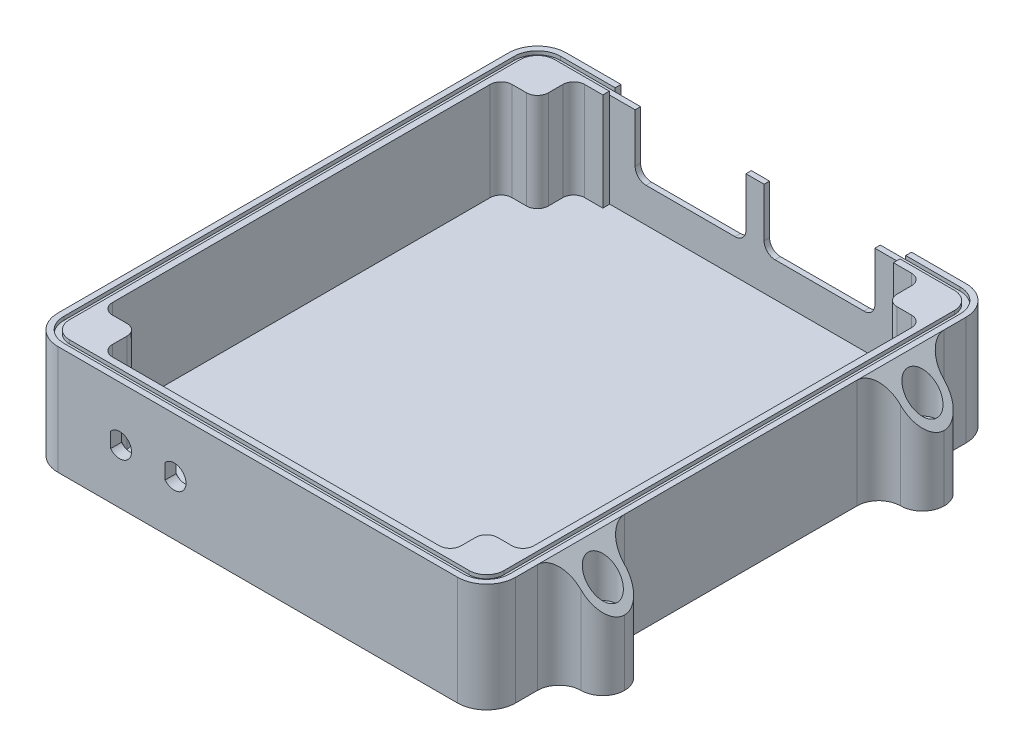
SolidWorks part; units mm, degrees
ref_plane "Front Plane" through (0, 0, 0) normal (0, 0, 1) x (1, 0, 0)
ref_plane "Top Plane" through (0, 0, 0) normal (0, 1, 0) x (1, 0, 0)
ref_plane "Right Plane" through (0, 0, 0) normal (1, 0, 0) x (0, 0, -1)
sketch "Sketch1" plane through (0, 0, 0) normal (0, 1, 0) x (1, 0, 0)
  line L0 (0, 0) -> (0, 94.0944) construction
  line L1 (-63, -70) -> (63, -70)
  line L2 (-63, -70) -> (-63, 70)
  line L3 (-63, 70) -> (63, 70)
  line L4 (63, -70) -> (63, 70)
  line L5 (-63, -70) -> (63, 70) construction
  line L6 (-63, 70) -> (63, -70) construction
  line L7 (63, -50) -> (75, -50)
  line L8 (63, -50) -> (63, -38)
  line L9 (63, -38) -> (75, -38)
  line L10 (75, -50) -> (75, -38)
  line L11 (0, 0) -> (-101.6778, 0) construction
  line L12 (-63, -38) -> (-75, -38)
  line L13 (-75, -50) -> (-75, -38)
  line L14 (-63, -50) -> (-75, -50)
  line L15 (-63, -50) -> (-63, -38)
  line L16 (63, 38) -> (75, 38)
  line L17 (75, 50) -> (75, 38)
  line L18 (63, 50) -> (75, 50)
  line L19 (63, 50) -> (63, 38)
  line L20 (-63, 50) -> (-63, 38)
  line L21 (-63, 50) -> (-75, 50)
  line L22 (-75, 50) -> (-75, 38)
  line L23 (-63, 38) -> (-75, 38)
  point P0 (0, 0)
  dimension "D1" = 140
  dimension "D2" = 126
  dimension "D3" = 12
  dimension "D4" = 12
  dimension "D5" = 20
extrude "Boss-Extrude2" add sketch "Sketch1" along normal blind 30 contours L14 L2 L12 L13 | L1 L4 L3 L2 | L23 L2 L21 L22 | L18 L4 L16 L17 | L7 L10 L9 L4 region at (0, 0, 0) region at (-69, 0, 44) region at (69, 0, 44) region at (-69, 0, -44) region at (69, 0, -44)
sketch "Sketch2" plane through (0, 30, 0) normal (0, 1, 0) x (1, 0, 0)
  line L1 (63, -50) -> (75, -50) construction
  line L3 (0, 0) -> (0, -57.1416) construction
  line L4 (0, 0) -> (45.0651, 0) construction
  line L5 (75, -50) -> (75, -38) construction
  point P0 (69, -44)
  point P5 (-69, -44)
  point P6 (69, 44)
  point P11 (-69, 44)
  dimension "D1" = 6
  dimension "D2" = 6
hole_wizard "CBORE for M4 Hex Socket Head Cap Screw1" positions "3DSketch1" profile "Sketch3" counterbore size "M4" standard "ISO" end condition through all
sketch3d "3DSketch1"
  point P0 (-69, 30, 44)
  point P3 (69, 30, 44)
  point P6 (69, 30, -44)
  point P9 (-69, 30, -44)
sketch "Sketch3" plane through (-69, 30, 44) normal (1, 0, 0) x (0, 0, 1)
  line L0 (0, 0) -> (0, 30)
  line L1 (2.4, 29.4) -> (3, 30)
  line L2 (2.4, 29.4) -> (2.4, 14.4)
  line L3 (2.4, 14.4) -> (4, 14.4)
  line L4 (4, 14.4) -> (4, 0)
  line L5 (4, 0) -> (0, 0)
  line L11 (0, -6.35) -> (0, 107.95) construction
  line L12 (3, 30) -> (0, 30)
  line L13 (-2.4, 29.4) -> (-3, 30) construction
  dimension "Thru Hole Dia." = 4.8
  dimension "Thru Hole Depth" = 30
  dimension "C'Bore Dia." = 8
  dimension "C'Bore Depth" = 14.4
  dimension "Far C'Sink Dia." = 6
  dimension "Far C'Sink Angle" = 90
chamfer "Chamfer1" distance 12 angle 45 4 edges at (-75, 30, 44) (-75, 30, -44) (75, 30, -44) (75, 30, 44)
fillet "Fillet1" radius 8 4 edges at (-63, 15, -70) (63, 15, -70) (63, 15, 70) (-63, 15, 70)
fillet "Fillet2" radius 6 16 edges at (-75, 9, -50) (-75, 9, 38) (-75, 9, 50) (-75, 9, -38) (75, 9, -50) (75, 9, -38) (75, 9, 38) (75, 9, 50) (-63, 15, 38) (-63, 15, -50) (-63, 15, -38) (-63, 15, 50) (63, 15, 38) (63, 15, -50) (63, 15, -38) (63, 15, 50)
sketch "Sketch6" plane through (0, 30, 0) normal (0, 1, 0) x (1, 0, 0)
  line L0 (-58, 52) -> (-58, -52)
  line L1 (-55, -55) -> (-51, -55)
  line L2 (-48, -58) -> (-48, -62)
  line L3 (-45, -65) -> (45, -65)
  line L4 (48, -62) -> (48, -58)
  line L5 (51, -55) -> (55, -55)
  line L6 (58, -52) -> (58, 52)
  line L7 (55, 55) -> (51, 55)
  line L8 (48, 58) -> (48, 62)
  line L9 (45, 65) -> (-45, 65)
  line L10 (-48, 62) -> (-48, 58)
  line L11 (-51, 55) -> (-55, 55)
  line L14 (-55, 70) -> (55, 70) construction
  line L15 (-55, -70) -> (55, -70) construction
  line L16 (63, -32) -> (63, 32) construction
  line L17 (-63, -32) -> (-63, 32) construction
  arc A0 (-45, 65) -> (-48, 62) centre (-45, 62) ccw
  arc A1 (-48, 58) -> (-51, 55) centre (-51, 58) cw
  arc A2 (-58, 52) -> (-55, 55) centre (-55, 52) cw
  arc A3 (48, 62) -> (45, 65) centre (45, 62) ccw
  arc A4 (51, 55) -> (48, 58) centre (51, 58) cw
  arc A5 (58, 52) -> (55, 55) centre (55, 52) ccw
  arc A6 (-58, -52) -> (-55, -55) centre (-55, -52) ccw
  arc A7 (-51, -55) -> (-48, -58) centre (-51, -58) cw
  arc A8 (55, -55) -> (58, -52) centre (55, -52) ccw
  arc A9 (48, -58) -> (51, -55) centre (51, -58) cw
  arc A10 (45, -65) -> (48, -62) centre (45, -62) ccw
  arc A11 (-45, -65) -> (-48, -62) centre (-45, -62) cw
  point P22 (-48, 65)
  point P25 (-48, 55)
  point P36 (-58, -55)
  point P39 (-48, -55)
  point P42 (58, -55)
  point P45 (48, -55)
  point P50 (-48, -65)
  dimension "D9" = 3
  dimension "D1" = 5
  dimension "D2" = 5
  dimension "D3" = 5
  dimension "D4" = 5
  dimension "D5" = 10
  dimension "D6" = 10
  dimension "D7" = 10
  dimension "D8" = 10
extrude "Cut-Extrude2" cut sketch "Sketch6" against normal blind 27
sketch "Sketch7" plane through (0, 30, 0) normal (0, 1, 0) x (1, 0, 0)
  line L12 (55, 66.8) -> (-55, 66.8)
  line L13 (-59.8, 62) -> (-59.8, 56)
  line L14 (-59.8, 56) -> (-59.8, 32)
  line L15 (-59.8, 32) -> (-59.8, -32)
  line L16 (-59.8, -32) -> (-59.8, -56)
  line L17 (-59.8, -56) -> (-59.8, -62)
  line L18 (-55, -66.8) -> (55, -66.8)
  line L19 (59.8, -62) -> (59.8, -56)
  line L20 (59.8, -56) -> (59.8, -32)
  line L21 (59.8, -32) -> (59.8, 32)
  line L22 (59.8, 32) -> (59.8, 56)
  line L23 (59.8, 56) -> (59.8, 62)
  line L24 (55, 68.4) -> (-55, 68.4)
  line L25 (-61.4, 62) -> (-61.4, 56)
  line L26 (-61.4, 56) -> (-61.4, 32)
  line L27 (-61.4, 32) -> (-61.4, -32)
  line L28 (-61.4, -32) -> (-61.4, -56)
  line L29 (-61.4, -56) -> (-61.4, -62)
  line L30 (-55, -68.4) -> (55, -68.4)
  line L31 (61.4, -62) -> (61.4, -56)
  line L32 (61.4, -56) -> (61.4, -32)
  line L33 (61.4, -32) -> (61.4, 32)
  line L34 (61.4, 32) -> (61.4, 56)
  line L35 (61.4, 56) -> (61.4, 62)
  line L36 (55, 68.4) -> (-55, 68.4)
  line L37 (-61.4, 62) -> (-61.4, 56)
  line L38 (-61.4, 56) -> (-61.4, 32)
  line L39 (-61.4, 32) -> (-61.4, -32)
  line L40 (-61.4, -32) -> (-61.4, -56)
  line L41 (-61.4, -56) -> (-61.4, -62)
  line L42 (-55, -68.4) -> (55, -68.4)
  line L43 (61.4, -62) -> (61.4, -56)
  line L44 (61.4, -56) -> (61.4, -32)
  line L45 (61.4, -32) -> (61.4, 32)
  line L46 (61.4, 32) -> (61.4, 56)
  line L47 (61.4, 56) -> (61.4, 62)
  arc A4 (-55, 66.8) -> (-59.8, 62) centre (-55, 62) ccw
  arc A5 (-59.8, -62) -> (-55, -66.8) centre (-55, -62) ccw
  arc A6 (55, -66.8) -> (59.8, -62) centre (55, -62) ccw
  arc A7 (59.8, 62) -> (55, 66.8) centre (55, 62) ccw
  arc A8 (-55, 68.4) -> (-61.4, 62) centre (-55, 62) ccw
  arc A9 (-61.4, -62) -> (-55, -68.4) centre (-55, -62) ccw
  arc A10 (55, -68.4) -> (61.4, -62) centre (55, -62) ccw
  arc A11 (61.4, 62) -> (55, 68.4) centre (55, 62) ccw
  arc A12 (-55, 68.4) -> (-61.4, 62) centre (-55, 62) ccw
  arc A13 (-61.4, -62) -> (-55, -68.4) centre (-55, -62) ccw
  arc A14 (55, -68.4) -> (61.4, -62) centre (55, -62) ccw
  arc A15 (61.4, 62) -> (55, 68.4) centre (55, 62) ccw
  dimension "D1" = 1.6
  dimension "D2" = 1.6
extrude "Cut-Extrude3" cut sketch "Sketch7" against normal blind 1
sketch "Sketch11" plane through (0, 0, -70) normal (0, 0, -1) x (-1, 0, 0)
  line L0 (0, 30) -> (-45.0651, 30) construction
  line L1 (-40, 30) -> (40, 30)
  line L2 (-40, 30) -> (-40, 5)
  line L3 (-40, 5) -> (40, 5)
  line L4 (40, 30) -> (40, 5)
  line L5 (55, 0) -> (55, 30) construction
  dimension "D1" = 80
  dimension "D2" = 25
  dimension "D3" = 15
extrude "Cut-Extrude4" cut sketch "Sketch11" against normal blind 1.6
sketch "Sketch12" plane through (0, 0, -65) normal (0, 0, 1) x (1, 0, 0)
  line L0 (45, 30) -> (-45, 30) construction
  line L1 (-40, 30) -> (40, 30)
  line L2 (-40, 30) -> (-40, 3)
  line L3 (-40, 3) -> (40, 3)
  line L4 (40, 30) -> (40, 3)
  line L5 (-45, 3) -> (-45, 30) construction
  dimension "D1" = 80
  dimension "D2" = 27
  dimension "D3" = 5
extrude "Cut-Extrude5" cut sketch "Sketch12" against normal blind 1.9
sketch "Sketch13" plane through (0, 0, -66.9) normal (0, 0, 1) x (1, 0, 0)
  line L0 (-40, 29) -> (40, 29) construction
  line L1 (-33, 29) -> (-2.5, 29)
  line L2 (-33, 29) -> (-33, 15.5)
  line L3 (-30, 12.5) -> (-5.5, 12.5)
  line L4 (-2.5, 29) -> (-2.5, 15.5)
  line L5 (0, 3) -> (0, 22.5584) construction
  line L6 (-40, 3) -> (40, 3) construction
  line L7 (30, 12.5) -> (5.5, 12.5)
  line L8 (2.5, 29) -> (2.5, 15.5)
  line L9 (33, 29) -> (2.5, 29)
  line L10 (33, 29) -> (33, 15.5)
  arc A0 (-5.5, 12.5) -> (-2.5, 15.5) centre (-5.5, 15.5) ccw
  arc A1 (-33, 15.5) -> (-30, 12.5) centre (-30, 15.5) ccw
  arc A2 (5.5, 12.5) -> (2.5, 15.5) centre (5.5, 15.5) cw
  arc A3 (33, 15.5) -> (30, 12.5) centre (30, 15.5) cw
  dimension "D1" = 3
  dimension "D2" = 30.5
  dimension "D3" = 16.5
  dimension "D4" = 2.5
extrude "Cut-Extrude6" cut sketch "Sketch13" against normal blind 1.9
sketch "Sketch14" plane through (0, 0, 65) normal (0, 0, -1) x (-1, 0, 0)
  line L1 (45, 3) -> (-45, 3) construction
  line L2 (45, 3) -> (45, 30) construction
  circle A0 centre (38, 15) radius 6
  circle A1 centre (23, 15) radius 6
  dimension "D1" = 12
  dimension "D3" = 12
  dimension "D4" = 7
  dimension "D5" = 2
extrude "Cut-Extrude8" cut sketch "Sketch14" against normal blind 2
sketch "Sketch16" plane through (0, 0, 67) normal (0, 0, -1) x (-1, 0, 0)
  line L0 (40.5, 17.0767) -> (40.5, 12.9233)
  line L1 (25.5, 17.0767) -> (25.5, 12.9233)
  circle A0 centre (38, 15) radius 3.25
  circle A1 centre (38, 15) radius 6 construction
  circle A2 centre (23, 15) radius 3.25
  dimension "D1" = 0
  dimension "D3" = 6.5
  dimension "D2" = 2.5
  dimension "D4" = 2
extrude "Cut-Extrude9" cut sketch "Sketch16" against normal blind 3 contours L1 A2 | L0 A0 region at (-37.8077, 15, 67) region at (-22.8077, 15, 67)
